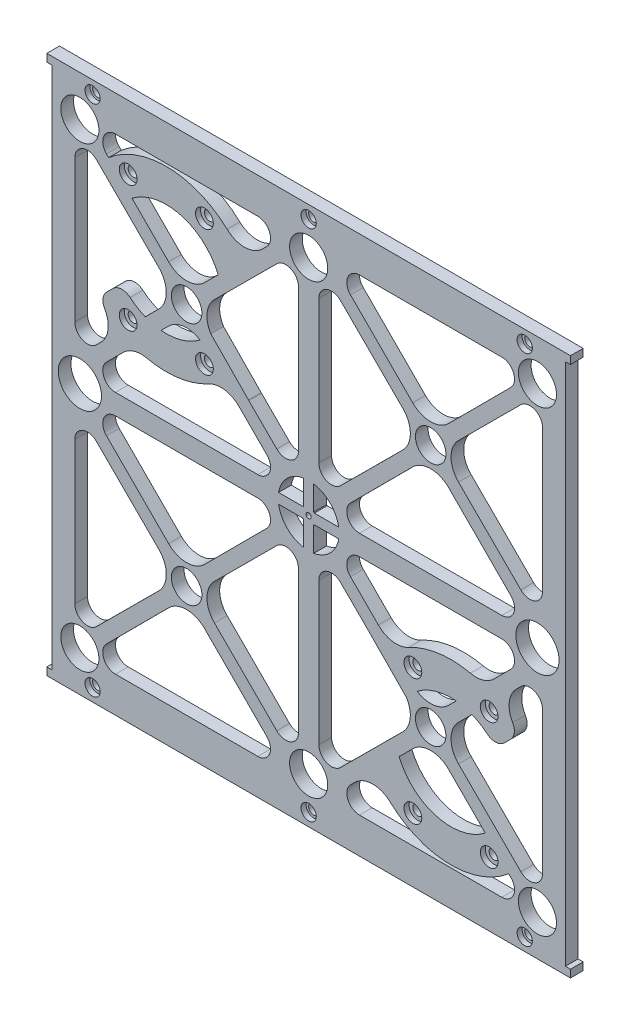
SolidWorks part; units mm, degrees
ref_plane "Přední rovina" through (0, 0, 0) normal (0, 0, 1) x (1, 0, 0)
ref_plane "Horní rovina" through (0, 0, 0) normal (0, 1, 0) x (1, 0, 0)
ref_plane "Pravá rovina" through (0, 0, 0) normal (1, 0, 0) x (0, 0, -1)
sketch "Skica1" plane through (0, 0, 0) normal (0, 0, 1) x (1, 0, 0)
  line L0 (0, 0) -> (103, 0) construction
  line L1 (0, 0) -> (0, 106) construction
  line L10 (-103, 106) -> (103, 106)
  line L19 (103, 106) -> (103, 0) construction
  line L20 (103, 106) -> (103, 103)
  line L21 (103, 103) -> (101, 103)
  line L22 (101, 103) -> (101, -103)
  line L23 (103, -103) -> (101, -103)
  line L24 (103, -106) -> (103, -103)
  line L25 (-103, -106) -> (103, -106)
  line L26 (-103, 103) -> (-101, 103)
  line L27 (-103, 106) -> (-103, 103)
  line L28 (-101, 103) -> (-101, -103)
  line L29 (-103, -103) -> (-101, -103)
  line L30 (-103, -106) -> (-103, -103)
  point P10 (101, 0)
  point P21 (0, -106)
  dimension "D1" = 206
  dimension "D2" = 212
  dimension "D3" = 3
  dimension "D4" = 2
extrude "Přidat vysunutím1" add sketch "Skica1" along normal blind 5 contours L29 L28 L26 L27 L10 L20 L21 L22 L23 L24 L25 L30
sketch "Skica2" plane through (0, 0, 5) normal (0, 0, 1) x (1, 0, 0)
  line L0 (0, 101) -> (-85, 101) construction
  line L1 (0, 0) -> (101, 0) construction
  line L2 (0, 0) -> (0, 101) construction
  line L3 (101, 103) -> (101, -103) construction
  circle A6 centre (-85, 101) radius 2
  circle A7 centre (0, 101) radius 2
  circle A8 centre (85, 101) radius 2
  circle A9 centre (-85, -101) radius 2
  circle A10 centre (0, -101) radius 2
  circle A11 centre (85, -101) radius 2
  dimension "D1" = 85
  dimension "D4" = 3
  dimension "D5" = 85
  dimension "D3" = 4
  dimension "D2" = 101
extrude "Odebrat vysunutím1" cut sketch "Skica2" against normal through all
sketch "Skica9" plane through (0, 0, 5) normal (0, 0, 1) x (1, 0, 0)
  line L0 (0, 0) -> (101, 0) construction
  circle A0 centre (-85, 101) radius 3
  circle A1 centre (0, 101) radius 3
  circle A2 centre (85, 101) radius 3
  circle A3 centre (85, -101) radius 3
  circle A4 centre (0, -101) radius 3
  circle A5 centre (-85, -101) radius 3
  dimension "D1" = 6
  dimension "D2" = 3
  dimension "D3" = 85
extrude "Odebrat vysunutím7" cut sketch "Skica9" against normal blind 2 and the other way through all
sketch "Skica4" plane through (0, 0, 5) normal (0, 0, 1) x (1, 0, 0)
  line L0 (0, 0) -> (48, 0) construction
  line L1 (48, 0) -> (48, 48) construction
  line L2 (48, 48) -> (48, 66) construction
  line L3 (48, 66) -> (48, 87) construction
  line L4 (48, 87) -> (20, 87) construction
  line L5 (40.9187, 58.9392) -> (16.4593, 83.4696)
  line L6 (55.0813, 58.9392) -> (79.5407, 83.4696)
  line L7 (20, 92) -> (76, 92)
  line L8 (48, 48) -> (-9, 105) construction
  line L10 (37.0608, 55.0813) -> (12.5304, 79.5407)
  line L11 (4, 76) -> (4, 20)
  line L12 (37.0608, 40.9187) -> (12.5304, 16.4593)
  line L13 (58.9392, 40.9187) -> (83.4696, 16.4593)
  line L14 (92, 76) -> (92, 20)
  line L15 (58.9392, 55.0813) -> (83.4696, 79.5407)
  line L16 (48, 48) -> (66, 48) construction
  line L20 (40.9187, 37.0608) -> (16.4593, 12.5304)
  line L21 (20, 4) -> (76, 4)
  line L22 (55.0813, 37.0608) -> (79.5407, 12.5304)
  line L23 (0, 0) -> (0, 103) construction
  line L24 (-40.9187, 58.9392) -> (-16.4593, 83.4696)
  line L25 (-20, 92) -> (-76, 92)
  line L26 (-55.0813, 58.9392) -> (-79.5407, 83.4696)
  line L27 (-58.9392, 55.0813) -> (-83.4696, 79.5407)
  line L28 (-92, 76) -> (-92, 20)
  line L29 (-58.9392, 40.9187) -> (-83.4696, 16.4593)
  line L30 (-55.0813, 37.0608) -> (-79.5407, 12.5304)
  line L31 (-20, 4) -> (-76, 4)
  line L32 (-40.9187, 37.0608) -> (-16.4593, 12.5304)
  line L33 (-37.0608, 40.9187) -> (-12.5304, 16.4593)
  line L34 (-4, 76) -> (-4, 20)
  line L35 (-37.0608, 55.0813) -> (-12.5304, 79.5407)
  line L36 (40.9187, -58.9392) -> (16.4593, -83.4696)
  line L37 (20, -92) -> (76, -92)
  line L38 (55.0813, -58.9392) -> (79.5407, -83.4696)
  line L39 (58.9392, -55.0813) -> (83.4696, -79.5407)
  line L40 (92, -76) -> (92, -20)
  line L41 (58.9392, -40.9187) -> (83.4696, -16.4593)
  line L42 (55.0813, -37.0608) -> (79.5407, -12.5304)
  line L43 (20, -4) -> (76, -4)
  line L44 (40.9187, -37.0608) -> (16.4593, -12.5304)
  line L45 (37.0608, -40.9187) -> (12.5304, -16.4593)
  line L46 (4, -76) -> (4, -20)
  line L47 (37.0608, -55.0813) -> (12.5304, -79.5407)
  line L48 (-37.0608, -55.0813) -> (-12.5304, -79.5407)
  line L49 (-4, -76) -> (-4, -20)
  line L50 (-37.0608, -40.9187) -> (-12.5304, -16.4593)
  line L51 (-55.0813, -58.9392) -> (-79.5407, -83.4696)
  line L52 (-20, -92) -> (-76, -92)
  line L53 (-40.9187, -58.9392) -> (-16.4593, -83.4696)
  line L54 (-58.9392, -40.9187) -> (-83.4696, -16.4593)
  line L55 (-92, -76) -> (-92, -20)
  line L56 (-58.9392, -55.0813) -> (-83.4696, -79.5407)
  line L57 (-40.9187, -37.0608) -> (-16.4593, -12.5304)
  line L58 (-20, -4) -> (-76, -4)
  line L59 (-55.0813, -37.0608) -> (-79.5407, -12.5304)
  circle A0 centre (48, 48) radius 6
  arc A1 (40.9187, 58.9392) -> (55.0813, 58.9392) centre (48, 66) ccw
  arc A2 (20, 92) -> (16.4593, 83.4696) centre (20, 87) ccw
  arc A3 (76, 92) -> (79.5407, 83.4696) centre (76, 87) cw
  arc A4 (4, 76) -> (12.5304, 79.5407) centre (9, 76) cw
  arc A5 (4, 20) -> (12.5304, 16.4593) centre (9, 20) ccw
  arc A6 (37.0608, 55.0813) -> (37.0608, 40.9187) centre (30, 48) cw
  arc A7 (58.9392, 55.0813) -> (58.9392, 40.9187) centre (66, 48) ccw
  arc A8 (92, 20) -> (83.4696, 16.4593) centre (87, 20) cw
  arc A9 (92, 76) -> (83.4696, 79.5407) centre (87, 76) ccw
  arc A10 (20, 4) -> (16.4593, 12.5304) centre (20, 9) cw
  arc A11 (76, 4) -> (79.5407, 12.5304) centre (76, 9) ccw
  arc A12 (40.9187, 37.0608) -> (55.0813, 37.0608) centre (48, 30) cw
  arc A13 (-20, 92) -> (-16.4593, 83.4696) centre (-20, 87) cw
  arc A14 (-76, 92) -> (-79.5407, 83.4696) centre (-76, 87) ccw
  arc A15 (-40.9187, 58.9392) -> (-55.0813, 58.9392) centre (-48, 66) cw
  circle A16 centre (-48, 48) radius 6
  arc A17 (-92, 76) -> (-83.4696, 79.5407) centre (-87, 76) cw
  arc A18 (-92, 20) -> (-83.4696, 16.4593) centre (-87, 20) ccw
  arc A19 (-58.9392, 55.0813) -> (-58.9392, 40.9187) centre (-66, 48) cw
  arc A20 (-40.9187, 37.0608) -> (-55.0813, 37.0608) centre (-48, 30) ccw
  arc A21 (-76, 4) -> (-79.5407, 12.5304) centre (-76, 9) cw
  arc A22 (-20, 4) -> (-16.4593, 12.5304) centre (-20, 9) ccw
  arc A23 (-37.0608, 55.0813) -> (-37.0608, 40.9187) centre (-30, 48) ccw
  arc A24 (-4, 20) -> (-12.5304, 16.4593) centre (-9, 20) cw
  arc A25 (-4, 76) -> (-12.5304, 79.5407) centre (-9, 76) ccw
  arc A26 (20, -92) -> (16.4593, -83.4696) centre (20, -87) cw
  arc A27 (76, -92) -> (79.5407, -83.4696) centre (76, -87) ccw
  arc A28 (40.9187, -58.9392) -> (55.0813, -58.9392) centre (48, -66) cw
  circle A29 centre (48, -48) radius 6
  arc A30 (92, -76) -> (83.4696, -79.5407) centre (87, -76) cw
  arc A31 (92, -20) -> (83.4696, -16.4593) centre (87, -20) ccw
  arc A32 (58.9392, -55.0813) -> (58.9392, -40.9187) centre (66, -48) cw
  arc A33 (40.9187, -37.0608) -> (55.0813, -37.0608) centre (48, -30) ccw
  arc A34 (76, -4) -> (79.5407, -12.5304) centre (76, -9) cw
  arc A35 (20, -4) -> (16.4593, -12.5304) centre (20, -9) ccw
  arc A36 (37.0608, -55.0813) -> (37.0608, -40.9187) centre (30, -48) ccw
  arc A37 (4, -20) -> (12.5304, -16.4593) centre (9, -20) cw
  arc A38 (4, -76) -> (12.5304, -79.5407) centre (9, -76) ccw
  arc A39 (-4, -76) -> (-12.5304, -79.5407) centre (-9, -76) cw
  arc A40 (-4, -20) -> (-12.5304, -16.4593) centre (-9, -20) ccw
  arc A41 (-37.0608, -55.0813) -> (-37.0608, -40.9187) centre (-30, -48) cw
  arc A42 (-40.9187, -58.9392) -> (-55.0813, -58.9392) centre (-48, -66) ccw
  arc A43 (-76, -92) -> (-79.5407, -83.4696) centre (-76, -87) cw
  arc A44 (-20, -92) -> (-16.4593, -83.4696) centre (-20, -87) ccw
  circle A45 centre (-48, -48) radius 6
  arc A46 (-58.9392, -55.0813) -> (-58.9392, -40.9187) centre (-66, -48) ccw
  arc A47 (-92, -20) -> (-83.4696, -16.4593) centre (-87, -20) cw
  arc A48 (-92, -76) -> (-83.4696, -79.5407) centre (-87, -76) ccw
  arc A49 (-20, -4) -> (-16.4593, -12.5304) centre (-20, -9) cw
  arc A50 (-76, -4) -> (-79.5407, -12.5304) centre (-76, -9) ccw
  arc A51 (-40.9187, -37.0608) -> (-55.0813, -37.0608) centre (-48, -30) cw
  dimension "D3" = 12
  dimension "D4" = 20
  dimension "D7" = 10
  dimension "D9" = 135
  dimension "D1" = 48
  dimension "D2" = 48
  dimension "D5" = 18
  dimension "D6" = 21
  dimension "D8" = 56
extrude "Odebrat vysunutím3" cut sketch "Skica4" against normal blind 10
sketch "Skica5" plane through (0, 0, 5) normal (0, 0, 1) x (1, 0, 0)
  line L0 (0, 0) -> (0, 103) construction
  line L2 (0, 0) -> (-85.5836, 85.5836) construction
  line L4 (0, 0) -> (58.9374, 58.9374) construction
  circle A4 centre (56, -56) radius 22
  circle A5 centre (56, -56) radius 35
  circle A8 centre (-56, 56) radius 22
  circle A9 centre (-56, 56) radius 35
  dimension "D1" = 70
  dimension "D3" = 44
  dimension "D4" = 56
  dimension "D5" = 56
  dimension "D6" = 45
  dimension "D2" = 45
extrude "Přidat vysunutím2" add sketch "Skica5" against normal blind 5
sketch "Skica6" plane through (0, 0, 5) normal (0, 0, 1) x (1, 0, 0)
  line L0 (56, -56) -> (56, -27) construction
  line L1 (56, -56) -> (85, -56) construction
  line L2 (-56, 56) -> (-56, 85) construction
  line L3 (-56, 56) -> (-27, 56) construction
  circle A0 centre (56, -56) radius 29 construction
  circle A1 centre (71, -31.1807) radius 3.5
  circle A2 centre (41, -31.1807) radius 3.5
  circle A3 centre (41, -80.8193) radius 3.5
  circle A4 centre (71, -80.8193) radius 3.5
  circle A10 centre (-56, 56) radius 35 construction
  circle A14 centre (56, -56) radius 35 construction
  circle A23 centre (-56, 56) radius 29 construction
  circle A24 centre (-41, 80.8193) radius 3.5
  circle A25 centre (-71, 80.8193) radius 3.5
  circle A26 centre (-71, 31.1807) radius 3.5
  circle A27 centre (-41, 31.1807) radius 3.5
  dimension "D1" = 58
  dimension "D2" = 7
  dimension "D4" = 70
  dimension "D5" = 58
  dimension "D7" = 15
  dimension "D6" = 7
  dimension "D8" = 70
  dimension "D3" = 15
extrude "Odebrat vysunutím4" cut sketch "Skica6" against normal blind 2 and the other way through all
sketch "Skica7" plane through (0, 0, 5) normal (0, 0, 1) x (1, 0, 0)
  circle A0 centre (41, -31.1807) radius 2
  circle A1 centre (71, -31.1807) radius 2
  circle A2 centre (41, -80.8193) radius 2
  circle A3 centre (71, -80.8193) radius 2
  circle A12 centre (-71, 80.8193) radius 2
  circle A13 centre (-41, 80.8193) radius 2
  circle A14 centre (-71, 31.1807) radius 2
  circle A15 centre (-41, 31.1807) radius 2
  dimension "D1" = 4
  dimension "D2" = 4
  dimension "D3" = 4
  dimension "D4" = 4
  dimension "D5" = 4
  dimension "D6" = 4
  dimension "D7" = 4
  dimension "D8" = 4
extrude "Odebrat vysunutím5" cut sketch "Skica7" against normal through all
fillet "Zaoblit1" radius 10 12 edges at (73.9487, -25.9526, 2.5) (68.7123, -23.3902, 2.5) (33.2675, -29.3874, 2.5) (29.3874, -33.2675, 2.5) (23.3902, -68.7123, 2.5) (25.9526, -73.9487, 2.5) (-68.7123, 23.3902, 2.5) (-33.2675, 29.3874, 2.5) (-29.3874, 33.2675, 2.5) (-23.3902, 68.7123, 2.5) (-25.9526, 73.9487, 2.5) (-73.9487, 25.9526, 2.5)
sketch "Skica8" plane through (0, 0, 5) normal (0, 0, 1) x (1, 0, 0)
  circle A0 centre (0, 0) radius 1
  dimension "D1" = 2
extrude "Odebrat vysunutím6" cut sketch "Skica8" against normal blind 10
sketch "Skica10" plane through (0, 0, 5) normal (0, 0, 1) x (1, 0, 0)
  line L0 (-23.5265, 27.4236) -> (-38.4779, 42.6967)
  line L1 (-38.4779, 42.6967) -> (-34.0947, 58.0388)
  line L2 (-34.0947, 58.0388) -> (-19.1533, 72.9369)
  line L3 (-19.1533, 72.9369) -> (-23.5265, 27.4236)
  line L4 (-82.634, 78.7075) -> (-73.3835, 69.4838)
  line L5 (-73.3835, 69.4838) -> (-73.3835, 42.5162)
  line L6 (-73.3835, 42.5162) -> (-82.6217, 33.2781)
  line L7 (-82.6217, 33.2781) -> (-92, 33.2781)
  line L9 (-92, 33.2781) -> (-92, 76)
  line L10 (-92, 76) -> (-82.634, 78.7075)
  line L11 (38.4779, -42.6967) -> (23.5265, -27.4236)
  line L12 (0, 0) -> (0, 88) construction
  line L13 (23.5265, -27.4236) -> (19.1533, -72.9369)
  line L14 (0, 0) -> (0, 101) construction
  line L15 (19.1533, -72.9369) -> (35.5777, -56.5601)
  line L16 (34.0947, -58.0388) -> (37.0608, -55.0813) construction
  line L17 (35.5777, -56.5601) -> (38.4779, -42.6967)
  line L18 (73.3835, -69.4838) -> (82.634, -78.7075)
  line L19 (82.634, -78.7075) -> (92, -76)
  line L20 (92, -76) -> (92, -33.2781)
  line L22 (92, -33.2781) -> (82.6217, -33.2781)
  line L23 (82.6217, -33.2781) -> (73.3835, -42.5162)
  line L24 (73.3835, -42.5162) -> (73.3835, -69.4838)
  line L25 (-90, 0) -> (0, 0) construction
  line L27 (2, 11.8322) -> (2, 2.2361)
  line L29 (-90, 0) -> (-90, -90) construction
  line L30 (-2, 11.8322) -> (-2, 2.2361)
  line L31 (-11.8322, 2) -> (-2.2361, 2)
  line L32 (-11.8322, -2) -> (-2.2361, -2)
  line L33 (-90, 0) -> (-90, 90) construction
  line L34 (-92, 76) -> (-92, 20) construction
  line L35 (11.8322, 2) -> (2.2361, 2)
  line L36 (92, -76) -> (92, -20) construction
  line L37 (-2, -11.8322) -> (-2, -2.2361)
  line L38 (2, -11.8322) -> (2, -2.2361)
  line L39 (11.8322, -2) -> (2.2361, -2)
  circle A0 centre (90, 0) radius 8.5
  arc A1 (-73.3835, 69.4838) -> (-64.2627, 35.6106) centre (-56, 56) ccw construction
  arc A2 (-82.634, 78.7075) -> (-81.5392, 32.0678) centre (-56, 56) ccw construction
  arc A3 (82.634, -78.7075) -> (81.5392, -32.0678) centre (56, -56) ccw construction
  arc A4 (73.3835, -69.4838) -> (64.2627, -35.6106) centre (56, -56) ccw construction
  circle A5 centre (-90, 0) radius 8.5
  circle A8 centre (-90, -90) radius 7.5
  circle A9 centre (90, -90) radius 7.5
  circle A10 centre (90, 90) radius 7.5
  circle A11 centre (-90, 90) radius 7.5
  arc A12 (2.2361, 2) -> (2, 2.2361) centre (0, 0) ccw
  circle A13 centre (0, 88) radius 7.5
  circle A14 centre (0, -88) radius 7.5
  arc A15 (2, -11.8322) -> (11.8322, -2) centre (0, 0) ccw
  arc A16 (-2, 2.2361) -> (-2.2361, 2) centre (0, 0) ccw
  arc A17 (-2, -2.2361) -> (-2.2361, -2) centre (0, 0) cw
  arc A18 (2.2361, -2) -> (2, -2.2361) centre (0, 0) cw
  arc A19 (-11.8322, -2) -> (-2, -11.8322) centre (0, 0) ccw
  arc A20 (-2, 11.8322) -> (-11.8322, 2) centre (0, 0) ccw
  arc A21 (11.8322, 2) -> (2, 11.8322) centre (0, 0) ccw
  point P23 (-92, 33.2781)
  point P42 (92, -33.2781)
  point P58 (0, 0)
  point P63 (-92, 48)
  point P66 (0, 0)
  point P76 (2, 18)
  point P78 (-92, 32.9336)
  point P80 (-92, 33.2781)
  point P96 (92, -48)
  point P98 (82.8127, -78.4962)
  point P99 (82.634, -78.7075)
  point P101 (-82.8127, 78.4962)
  point P102 (-82.634, 78.7075)
  dimension "D3" = 17
  dimension "D5" = 15
  dimension "D7" = 15
  dimension "D9" = 2
  dimension "D12" = 180
  dimension "D13" = 24
  dimension "D14" = 6
  dimension "D15" = 15
  dimension "D1" = 45
  dimension "D2" = 225
  dimension "D4" = 90
  dimension "D6" = 88
  dimension "D8" = 90
  dimension "D11" = 180
  dimension "D16" = 4
  dimension "D17" = 4
  dimension "D10" = 2
extrude "Odebrat vysunutím8" cut sketch "Skica10" against normal through all
fillet "Zaoblit2" radius 5 4 edges at (82.6217, -33.2781, 2.5) (73.3835, -42.5162, 2.5) (-73.3835, 42.5162, 2.5) (-82.6217, 33.2781, 2.5)
